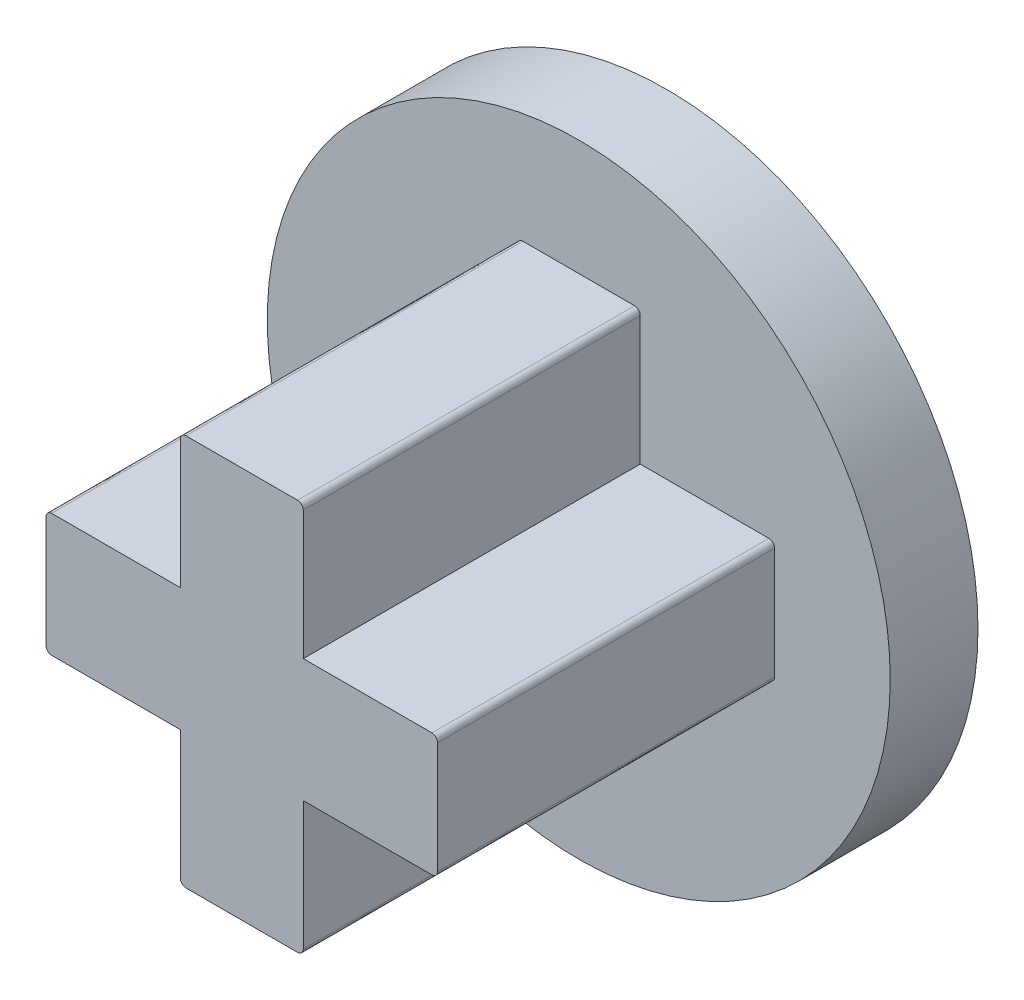
SolidWorks part; units mm, degrees
ref_plane "Front Plane" through (0, 0, 0) normal (0, 0, 1) x (1, 0, 0)
ref_plane "Top Plane" through (0, 0, 0) normal (0, 1, 0) x (1, 0, 0)
ref_plane "Right Plane" through (0, 0, 0) normal (1, 0, 0) x (0, 0, -1)
sketch "Sketch1" plane through (0, 0, 0) normal (0, 0, 1) x (1, 0, 0)
  circle A0 centre (0, 0) radius 11
  dimension "D1" = 22
extrude "Boss-Extrude1" add sketch "Sketch1" along normal blind 15
sketch "Sketch2" plane through (0, 0, 15) normal (0, 0, 1) x (1, 0, 0)
  line L0 (-2.3717, -7.1151) -> (-2.3717, -2.3717) construction
  line L1 (-2.3717, 7.1151) -> (2.3717, 7.1151) construction
  line L2 (2.3717, 7.1151) -> (2.3717, 2.3717) construction
  line L3 (2.3717, -7.1151) -> (-2.3717, -7.1151) construction
  line L4 (7.1151, 2.3717) -> (2.3717, 2.3717) construction
  line L5 (-7.1151, 2.3717) -> (-7.1151, -2.3717) construction
  line L6 (-7.1151, -2.3717) -> (-2.3717, -2.3717) construction
  line L7 (7.1151, -2.3717) -> (7.1151, 2.3717) construction
  line L8 (2.3717, -2.3717) -> (7.1151, -2.3717) construction
  line L9 (-2.3717, 2.3717) -> (-2.3717, 7.1151) construction
  line L10 (-2.3717, 2.3717) -> (-7.1151, 2.3717) construction
  line L11 (2.3717, -2.3717) -> (2.3717, -7.1151) construction
  line L12 (-2.1717, 2.1717) -> (-6.9151, 2.1717)
  line L13 (-6.9151, 2.1717) -> (-6.9151, -2.1717)
  line L14 (-6.9151, -2.1717) -> (-2.1717, -2.1717)
  line L15 (-2.1717, -6.9151) -> (-2.1717, -2.1717)
  line L16 (2.1717, -6.9151) -> (-2.1717, -6.9151)
  line L17 (2.1717, -2.1717) -> (2.1717, -6.9151)
  line L18 (2.1717, -2.1717) -> (6.9151, -2.1717)
  line L19 (6.9151, -2.1717) -> (6.9151, 2.1717)
  line L20 (6.9151, 2.1717) -> (2.1717, 2.1717)
  line L21 (2.1717, 6.9151) -> (2.1717, 2.1717)
  line L22 (-2.1717, 6.9151) -> (2.1717, 6.9151)
  line L23 (-2.1717, 2.1717) -> (-2.1717, 6.9151)
  circle A1 centre (0, 0) radius 11 construction
  circle A2 centre (0, 0) radius 7.5
  circle A3 centre (0, 0) radius 7.5 construction
  circle A4 centre (0, 0) radius 11
  dimension "D1" = 3.5
  dimension "D2" = 0.2
extrude "Cut-Extrude1" cut sketch "Sketch2" against normal blind 11.9
fillet "Fillet1" radius 0.2 8 edges at (-6.9151, 2.1717, 9.05) (-6.9151, -2.1717, 9.05) (-2.1717, -6.9151, 9.05) (2.1717, -6.9151, 9.05) (6.9151, -2.1717, 9.05) (6.9151, 2.1717, 9.05) (2.1717, 6.9151, 9.05) (-2.1717, 6.9151, 9.05) conic rho 0.4
